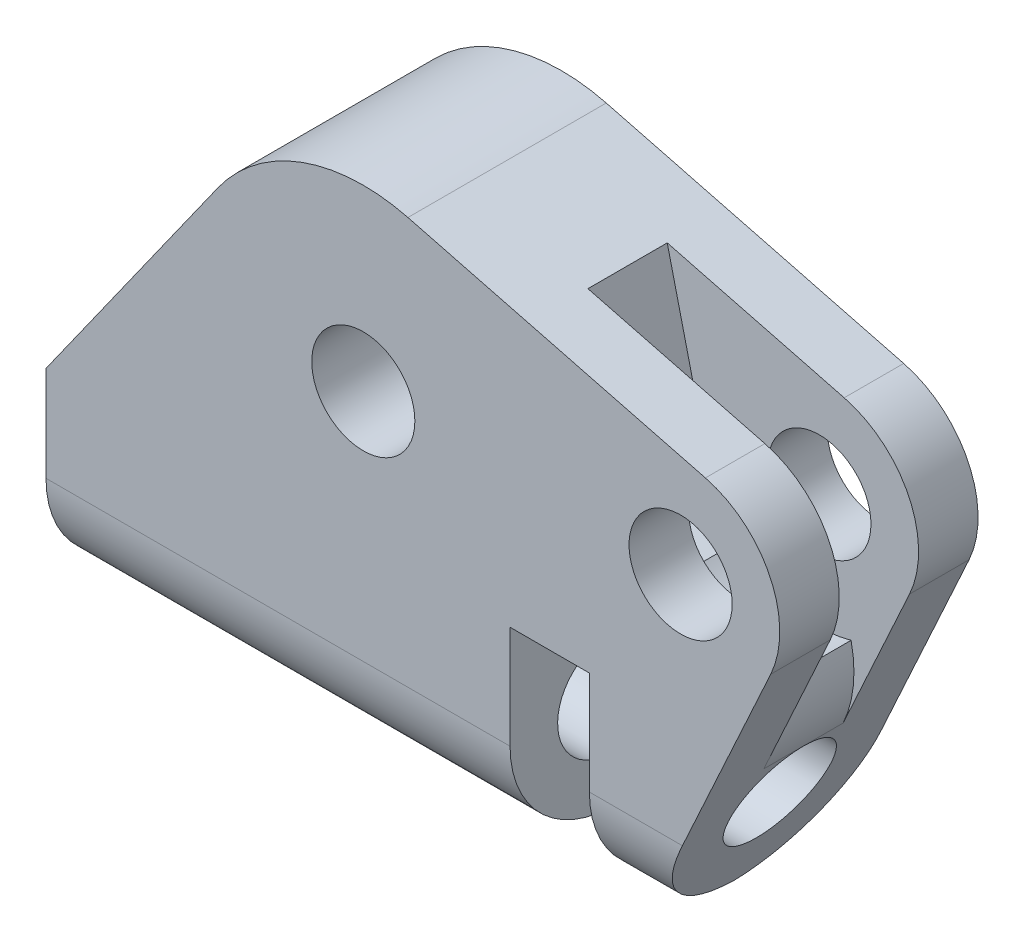
SolidWorks part; units mm, degrees
material "ABS"
ref_plane "Front Plane" through (0, 0, 0) normal (0, 0, 1) x (1, 0, 0)
ref_plane "Top Plane" through (0, 0, 0) normal (0, 1, 0) x (1, 0, 0)
ref_plane "Right Plane" through (0, 0, 0) normal (1, 0, 0) x (0, 0, -1)
sketch "Sketch1" plane through (0, 0, 0) normal (0, 0, 1) x (1, 0, 0)
  circle A1 centre (434.9497, -853.4014) radius 6.5
  circle A2 centre (434.9497, -853.4014) radius 22.5
  dimension "D1" = 45
extrude "Boss-Extrude1" add sketch "Sketch1" along normal mid plane 25
sketch "Sketch2" plane through (0, 0, 0) normal (0, 0, 1) x (1, 0, 0)
  line L0 (440.5747, -831.6159) -> (478.0747, -841.2983)
  line L1 (474.9497, -853.4014) -> (434.9497, -853.4014) construction
  line L2 (394.9497, -883.4014) -> (474.9497, -883.4014) construction
  line L3 (474.9497, -883.4014) -> (486.3129, -858.6097)
  line L4 (394.9497, -870.9014) -> (394.9497, -895.9014)
  line L5 (394.9497, -870.9014) -> (416.5981, -840.3834)
  line L6 (394.9497, -895.9014) -> (469.2203, -895.9014)
  line L7 (469.2203, -895.9014) -> (474.9497, -883.4014)
  line L8 (404.9497, -895.9014) -> (404.9497, -856.8043) construction
  circle A0 centre (434.9497, -853.4014) radius 22.5 construction
  arc A1 (440.5747, -831.6159) -> (416.5981, -840.3834) centre (434.9497, -853.4014) ccw
  arc A2 (486.3129, -858.6097) -> (478.0747, -841.2983) centre (474.9497, -853.4014) ccw
  circle A3 centre (474.9497, -853.4014) radius 6.5
  circle A4 centre (434.9497, -853.4014) radius 6.5 construction
  circle A5 centre (434.9497, -853.4014) radius 6.5
  point P10 (434.9497, -883.4014)
  point P13 (394.9497, -883.4014)
  dimension "D1" = 25
  dimension "D2" = 13
  dimension "D3" = 40
  dimension "D4" = 30
  dimension "D5" = 25
  dimension "D6" = 10
extrude "Boss-Extrude2" add sketch "Sketch2" along normal mid plane 25
sketch "Sketch3" plane through (394.9497, 0, 0) normal (-1, 0, 0) x (0, 0, 1)
  line L0 (12.5, -883.4014) -> (-12.5, -883.4014) construction
  line L1 (12.5, -870.9014) -> (12.5, -895.9014) construction
  line L2 (-12.5, -870.9014) -> (-12.5, -895.9014) construction
  circle A0 centre (0, -883.4014) radius 6.5
  dimension "D1" = 13
extrude "Cut-Extrude1" cut sketch "Sketch3" against normal through all
fillet "Fillet1" radius 13 2 edges at (432.085, -895.9014, -12.5) (432.085, -895.9014, 12.5)
sketch "Sketch4" plane through (0, 0, 12.5) normal (0, 0, 1) x (1, 0, 0)
  line L0 (453.4497, -882.9014) -> (468.4497, -882.9014) construction
  line L1 (453.4497, -882.9014) -> (453.4497, -895.8918) construction
  line L2 (468.4497, -882.9014) -> (468.4497, -895.8918) construction
  line L3 (453.4497, -895.8918) -> (468.4497, -895.8918) construction
  line L4 (394.9497, -882.9014) -> (475.1789, -882.9014) construction
  line L5 (469.2247, -895.8918) -> (394.9497, -895.8918) construction
  line L6 (468.4497, -882.9014) -> (468.4497, -869.911) construction
  line L7 (468.4497, -869.911) -> (453.4497, -869.911) construction
  line L8 (453.4497, -869.911) -> (453.4497, -882.9014) construction
  line L9 (468.4497, -853.4014) -> (468.4497, -832.159) construction
  line L10 (463.4497, -869.911) -> (463.4497, -895.8918)
  line L11 (463.4497, -895.8918) -> (453.4497, -895.8918)
  line L12 (453.4497, -895.8918) -> (453.4497, -869.911)
  line L13 (453.4497, -869.911) -> (463.4497, -869.911)
  circle A1 centre (474.9497, -853.4014) radius 6.5 construction
  dimension "D1" = 5
  dimension "D2" = 10
extrude "Cut-Extrude2" cut sketch "Sketch4" against normal through all
sketch "Sketch5" plane through (0, 0, 0) normal (0, 0, 1) x (1, 0, 0)
  line L0 (478.0747, -841.2983) -> (440.5747, -831.6159) construction
  line L1 (470.9596, -839.4612) -> (455.7671, -835.5385)
  line L2 (460.8476, -856.7751) -> (455.7671, -835.5385)
  circle A0 centre (474.9497, -853.4014) radius 6.5 construction
  circle A1 centre (474.9497, -853.4014) radius 6.5
  arc A2 (460.8476, -856.7751) -> (470.9596, -839.4612) centre (474.9497, -853.4014) ccw
  circle A3 centre (474.9497, -853.4014) radius 14.5 construction
  dimension "D2" = 21.2365
  dimension "D1" = 8
extrude "Cut-Extrude3" cut sketch "Sketch5" against normal mid plane 10
sketch "Sketch6" plane through (-173.7662, -672.9937, 0) normal (0.25, 0.9682, 0) x (0.9682, -0.25, 0)
  line L0 (684.2283, 5) -> (684.2283, -5) construction
  line L1 (660.4076, 5) -> (660.4076, -5) construction
  line L2 (684.2283, 5) -> (684.2283, -5) construction
  line L3 (660.4076, 5) -> (660.4076, -5) construction
  line L4 (660.4076, 5) -> (660.4076, -5)
  line L5 (660.4076, 5) -> (684.2283, 5)
  line L6 (660.4076, -5) -> (684.2283, -5)
  line L7 (684.2283, 5) -> (684.2283, -5)
extrude "Cut-Extrude4" cut sketch "Sketch6" against normal blind 25
fillet "Fillet2" radius 15 1 edges at (481.954, -868.1198, 0)
